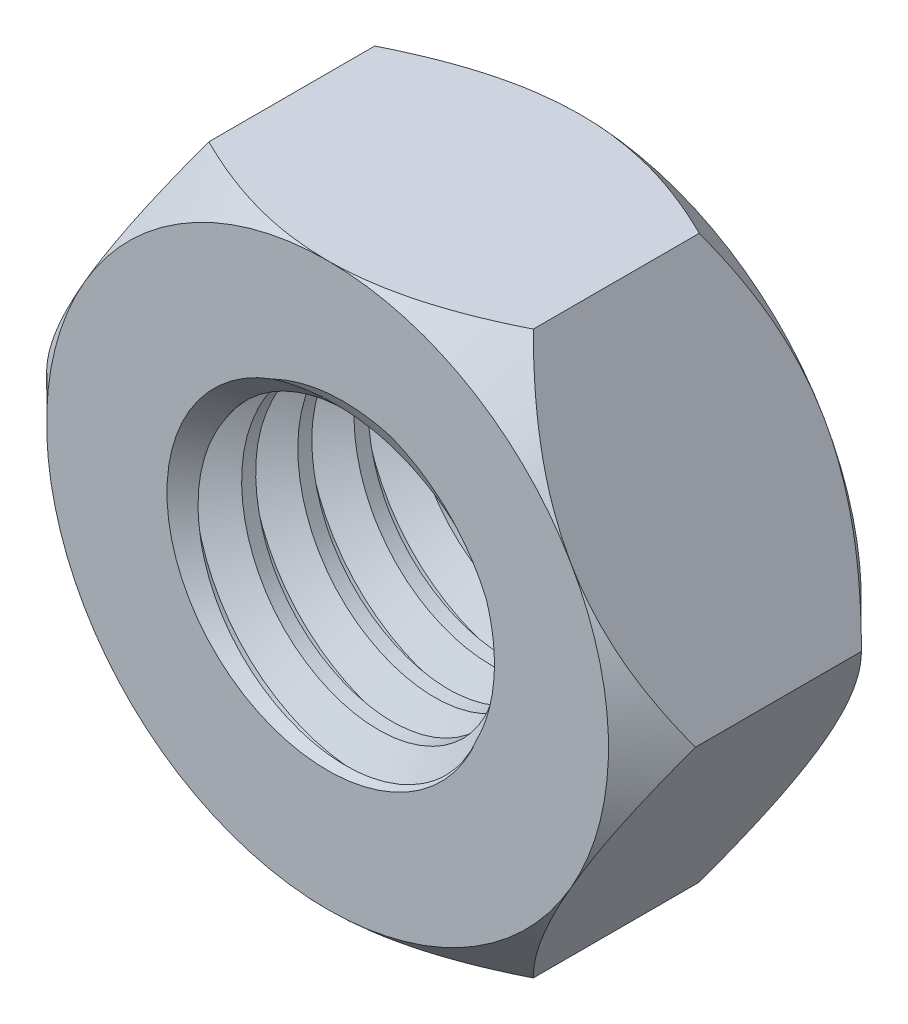
SolidWorks part; units mm, degrees
material "AISI 1020"
ref_plane "Front Plane" through (0, 0, 0) normal (0, 0, 1) x (1, 0, 0)
ref_plane "Top Plane" through (0, 0, 0) normal (0, 1, 0) x (1, 0, 0)
ref_plane "Right Plane" through (0, 0, 0) normal (1, 0, 0) x (0, 0, -1)
sketch "Sketch1" plane through (0, 0, 0) normal (0, 0, 1) x (1, 0, 0)
  line L1 (1.7321, -3) -> (3.4641, 0)
  line L2 (3.4641, 0) -> (1.7321, 3)
  line L3 (1.7321, 3) -> (-1.7321, 3)
  line L4 (-1.7321, 3) -> (-3.4641, 0)
  line L5 (-3.4641, 0) -> (-1.7321, -3)
  line L6 (-1.7321, -3) -> (1.7321, -3)
  circle A0 centre (0, 0) radius 3 construction
  dimension "D1" = 6
extrude "Boss-Extrude1" add sketch "Sketch1" along normal mid plane 2.7
sketch "Sketch2" plane through (0, 0, 1.35) normal (0, 0, 1) x (1, 0, 0)
  line L0 (-1.7321, 3) -> (-3.4641, 0) construction
  circle A0 centre (0, 0) radius 3
extrude "Cut-Extrude1" cut sketch "Sketch2" against normal through all draft 45 flip side to cut
mirror "Mirror1" about plane through (0, 0, 0) normal (0, 0, 1) of "Cut-Extrude1"
sketch "Sketch3" plane through (0, 0, 1.35) normal (0, 0, 1) x (1, 0, 0)
  circle A0 centre (0, 0) radius 1.515
  dimension "D1" = 3.03
extrude "Cut-Extrude2" cut sketch "Sketch3" against normal through all
chamfer "Chamfer1" distance 0.2 angle 45 2 edges at (1.515, 0, -1.35) (1.515, 0, 1.35)
thread "Thread1" pitch 0.6 method cut profile "Thread Profile1" start angle 0, offset 2, length 0, pitch 0.6, diameter 3.03
ref_plane "Plane1" through (1.515, 0, -3.15) normal (0, -1, 0) x (1, 0, 0)
sketch "Thread Profile1" plane through (1.515, 0, -3.15) normal (0, -1, 0) x (1, 0, 0)
  line L0 (0, 0) -> (0, 0.6) construction
  line L1 (0, 0) -> (0.3248, 0.1875)
  line L2 (0.3248, 0.1875) -> (0.3248, 0.2625)
  line L3 (0.3248, 0.2625) -> (0, 0.45)
  line L4 (0.3248, 0.225) -> (0, 0.225) construction
  line L11 (0, 0) -> (0, 0.45)
  point P2 (0, 0)
  dimension "Pitch" = 0.6
  dimension "Profile_Angle" = 60
  dimension "Profile_Land" = 0.075
  dimension "Profile_Height" = 0.3248
ref_axis "Axis1" through (0, 0, -0.8688) along (0, 0, 1)
